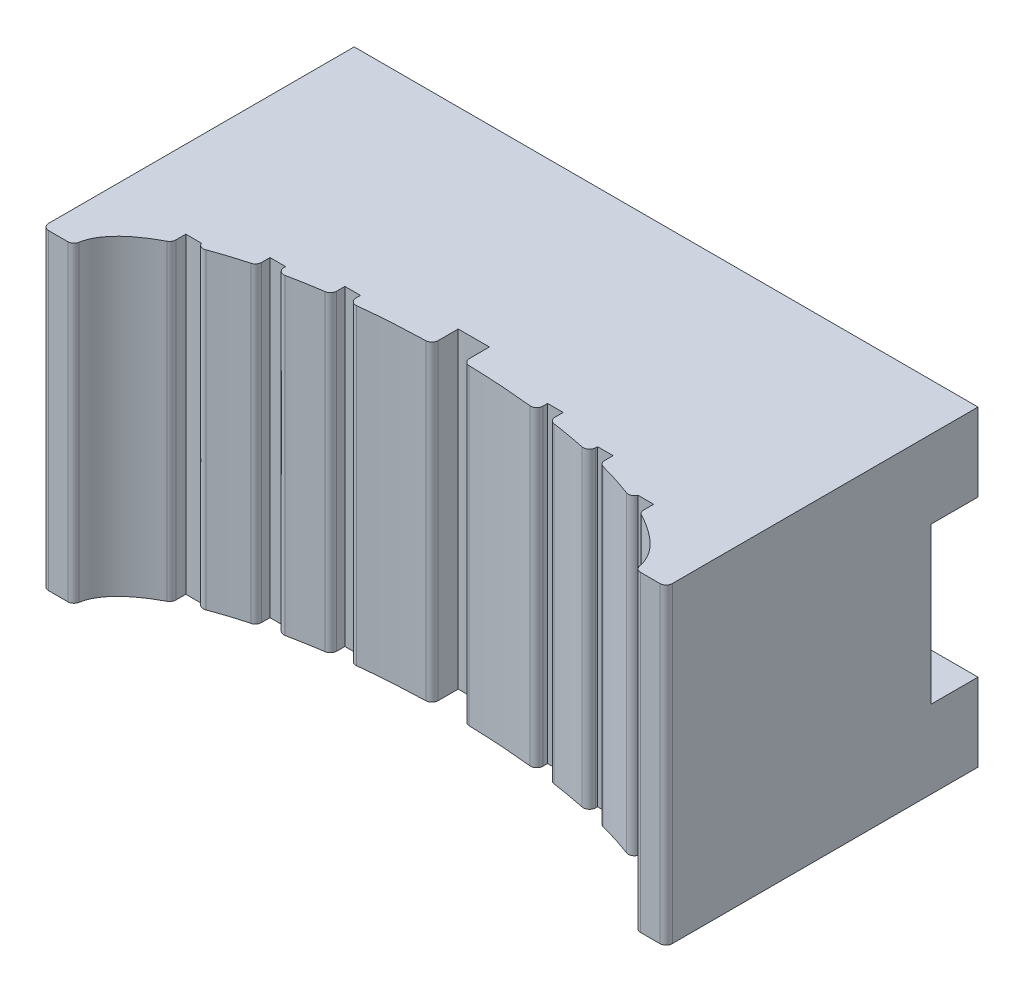
SolidWorks part; units mm, degrees
ref_plane "Ebene vorne" through (0, 0, 0) normal (0, 0, 1) x (1, 0, 0)
ref_plane "Ebene oben" through (0, 0, 0) normal (0, 1, 0) x (1, 0, 0)
ref_plane "Ebene rechts" through (0, 0, 0) normal (1, 0, 0) x (0, 0, -1)
sketch "Skizze1" plane through (0, 0, 0) normal (0, 0, 1) x (1, 0, 0)
  line L1 (-20, 7.3469) -> (0, 7.3469)
  line L2 (-20, 7.3469) -> (-20, -2.6531)
  line L3 (-20, -2.6531) -> (0, -2.6531)
  line L4 (0, 7.3469) -> (0, -2.6531)
  line L5 (-20, 7.3469) -> (0, -2.6531) construction
  line L6 (-20, -2.6531) -> (0, 7.3469) construction
  point P0 (-10, 2.3469)
  dimension "D1" = 10
  dimension "D2" = 20
extrude "Aufsatz-Linear austragen1" add sketch "Skizze1" along normal blind 10
sketch "Skizze3" plane through (0, 0, 0) normal (0, 0, -1) x (-1, 0, 0)
  line L0 (0, -2.6531) -> (0, 7.3469) construction
  line L1 (12.05, 3.2969) -> (7.95, 3.2969)
  line L2 (12.05, 3.2969) -> (12.05, 1.3969)
  line L3 (12.05, 1.3969) -> (7.95, 1.3969)
  line L4 (7.95, 3.2969) -> (7.95, 1.3969)
  line L5 (12.05, 3.2969) -> (7.95, 1.3969) construction
  line L6 (12.05, 1.3969) -> (7.95, 3.2969) construction
  line L7 (20, -2.6531) -> (0, -2.6531) construction
  point P0 (10, 2.3469)
  dimension "D1" = 1.9
  dimension "D2" = 4.1
  dimension "D3" = 10
  dimension "D4" = 5
extrude "Schnitt-Linear austragen2" cut sketch "Skizze3" against normal blind 5
sketch "Skizze9" plane through (0, 7.3469, 0) normal (0, 1, 0) x (1, 0, 0)
  line L2 (-20, -10) -> (-20, 0) construction
  ellipse E1 centre (-10, -10) end of major axis (-1, -10) minor radius 3
  point P0 (0, 0)
  point P3 (0, 0)
  point P4 (0, 0)
  point P5 (0, -5.221)
  point P6 (-20, -6.4491)
  point P7 (0, 0)
  point P13 (0, 0)
  point P14 (0, 0)
  point P15 (0, 0)
  point P17 (0, 0)
  dimension "D1" = 10
  dimension "D2" = 3
extrude "Schnitt-Linear austragen3" cut sketch "Skizze9" against normal blind 10
sketch "Skizze10" plane through (0, 0, 0) normal (0, 0, -1) x (-1, 0, 0)
  line L0 (12.05, 1.3969) -> (12.05, 3.2969) construction
  line L1 (13.05, -0.4786) -> (20, -0.4786)
  line L2 (13.05, -0.4786) -> (13.05, 4.5214)
  line L3 (13.05, 4.5214) -> (20, 4.5214)
  line L4 (20, -0.4786) -> (20, 4.5214)
  line L5 (13.05, -0.4786) -> (20, 4.5214) construction
  line L6 (13.05, 4.5214) -> (20, -0.4786) construction
  line L7 (20, 7.3469) -> (20, -2.6531) construction
  point P0 (16.525, 2.0214)
  dimension "D1" = 5
  dimension "D2" = 1
  dimension "D3" = 0
  dimension "D4" = 6.95
extrude "Schnitt-Linear austragen4" cut sketch "Skizze10" against normal blind 1.5
sketch "Skizze11" plane through (0, 0, 0) normal (0, 0, -1) x (-1, 0, 0)
  line L0 (0, -2.6531) -> (0, 7.3469) construction
  line L1 (7, -0.1531) -> (0, -0.1531)
  line L2 (7, -0.1531) -> (7, 4.8469)
  line L3 (7, 4.8469) -> (0, 4.8469)
  line L4 (0, -0.1531) -> (0, 4.8469)
  line L5 (7, -0.1531) -> (0, 4.8469) construction
  line L6 (7, 4.8469) -> (0, -0.1531) construction
  line L7 (0, 7.3469) -> (20, 7.3469) construction
  point P0 (3.5, 2.3469)
  dimension "D1" = 5
  dimension "D2" = 7
  dimension "D3" = 0
  dimension "D4" = 2.5
extrude "Schnitt-Linear austragen5" cut sketch "Skizze11" against normal blind 1.5
sketch "Skizze13" plane through (0, -2.6531, 0) normal (0, -1, 0) x (1, 0, 0)
  line L0 (0, 10) -> (0, 0) construction
  line L1 (-10.5, 7.1658) -> (-9.5, 7.1658)
  line L2 (-10.5, 7.1658) -> (-10.5, 6.1658)
  line L3 (-10.5, 6.1658) -> (-9.5, 6.1658)
  line L4 (-9.5, 7.1658) -> (-9.5, 6.1658)
  line L5 (-10.5, 7.1658) -> (-9.5, 6.1658) construction
  line L6 (-10.5, 6.1658) -> (-9.5, 7.1658) construction
  point P0 (-10, 6.6658)
  dimension "D1" = 1
  dimension "D2" = 1
  dimension "D3" = 9.5
extrude "Schnitt-Linear austragen7" cut sketch "Skizze13" against normal blind 10
sketch "Skizze14" plane through (0, -2.6531, 0) normal (0, -1, 0) x (1, 0, 0)
  line L0 (-10.5, 7.0046) -> (-10.5, 6.1658) construction
  line L1 (-15.5, 7.7) -> (-15, 7.7)
  line L2 (-15.5, 7.7) -> (-15.5, 7.2)
  line L3 (-15.5, 7.2) -> (-15, 7.2)
  line L4 (-15, 7.7) -> (-15, 7.2)
  line L5 (-15.5, 7.7) -> (-15, 7.2) construction
  line L6 (-15.5, 7.2) -> (-15, 7.7) construction
  line L8 (-5, 7.7) -> (-4.5, 7.7)
  line L9 (-5, 7.7) -> (-5, 7.2)
  line L10 (-5, 7.2) -> (-4.5, 7.2)
  line L11 (-4.5, 7.7) -> (-4.5, 7.2)
  line L12 (-5, 7.7) -> (-4.5, 7.2) construction
  line L13 (-5, 7.2) -> (-4.5, 7.7) construction
  line L14 (-13.5, 7.3) -> (-13, 7.3)
  line L15 (-9.5, 6.1658) -> (-9.5, 7.0046) construction
  line L16 (-3, 8.4) -> (-2.5, 8.4)
  line L17 (-3, 8.4) -> (-3, 7.9)
  line L18 (-3, 7.9) -> (-2.5, 7.9)
  line L19 (-2.5, 8.4) -> (-2.5, 7.9)
  line L20 (-3, 8.4) -> (-2.5, 7.9) construction
  line L21 (-3, 7.9) -> (-2.5, 8.4) construction
  line L26 (-17.5, 8.4) -> (-17, 8.4)
  line L27 (-17.5, 8.4) -> (-17.5, 7.9)
  line L28 (-17.5, 7.9) -> (-17, 7.9)
  line L29 (-17, 8.4) -> (-17, 7.9)
  line L30 (-17.5, 8.4) -> (-17, 7.9) construction
  line L31 (-17.5, 7.9) -> (-17, 8.4) construction
  line L32 (-13.5, 7.3) -> (-13.5, 6.8)
  line L33 (-13.5, 6.8) -> (-13, 6.8)
  line L34 (-13, 7.3) -> (-13, 6.8)
  line L35 (-13.5, 7.3) -> (-13, 6.8) construction
  line L36 (-13.5, 6.8) -> (-13, 7.3) construction
  line L37 (-7, 7.3) -> (-6.5, 7.3)
  line L38 (-7, 7.3) -> (-7, 6.8)
  line L39 (-7, 6.8) -> (-6.5, 6.8)
  line L40 (-6.5, 7.3) -> (-6.5, 6.8)
  line L41 (-7, 7.3) -> (-6.5, 6.8) construction
  line L42 (-7, 6.8) -> (-6.5, 7.3) construction
  line L44 (-1, 10) -> (0, 10) construction
  line L45 (-20, 10) -> (-19, 10) construction
  ellipse E0 centre (-10, 10) end of major axis (-1, 10) minor radius 3 (-19, 10) -> (-10.5, 7.0046) ccw construction
  point P0 (-15.25, 7.25)
  point P7 (-10.5, 6.5852)
  point P10 (-17.25, 8.15)
  point P11 (-4.75, 7.45)
  point P18 (-9.5, 6.5852)
  point P19 (-2.75, 8.15)
  point P28 (-13.25, 7.05)
  point P33 (-6.75, 7.05)
  point P38 (-5, 7.45)
  point P48 (-0.5, 10)
  dimension "D2" = 0.5
  dimension "D3" = 4.5
  dimension "D4" = 0.5
  dimension "D5" = 4.5
  dimension "D6" = 2.3
  dimension "D7" = 0.5
  dimension "D8" = 1.5
  dimension "D9" = 0.5
  dimension "D10" = 2.3
  dimension "D11" = 2.7
  dimension "D12" = 1.6
  dimension "D13" = 0.5
  dimension "D14" = 1.5
  dimension "D15" = 1.6
  dimension "D16" = 0.5
  dimension "D17" = 0.5
  dimension "D18" = 2.7
extrude "Schnitt-Linear austragen8" cut sketch "Skizze14" against normal blind 10
fillet "Verrundung2" radius 0.2 4 edges at (-13.5, 2.3469, 7.2361) (-15.5, 2.3469, 7.6254) (-17.5, 2.3469, 8.3417) (-19, 2.3469, 10)
fillet "Verrundung3" radius 0.2 3 edges at (-17, 2.3469, 8.1144) (-15, 2.3469, 7.5056) (-13, 2.3469, 7.1716)
fillet "Verrundung4" radius 0.2 7 edges at (-1, 2.3469, 10) (-7, 2.3469, 7.1716) (-3, 2.3469, 8.1144) (-5, 2.3469, 7.5056) (-6.5, 2.3469, 7.2361) (-4.5, 2.3469, 7.6254) (-2.5, 2.3469, 8.3417)
fillet "Verrundung5" radius 0.2 2 edges at (-9.5, 2.3469, 7.0046) (-10.5, 2.3469, 7.0046)
fillet "Verrundung6" radius 0.2 2 edges at (-20, 2.3469, 10) (0, 2.3469, 10)
